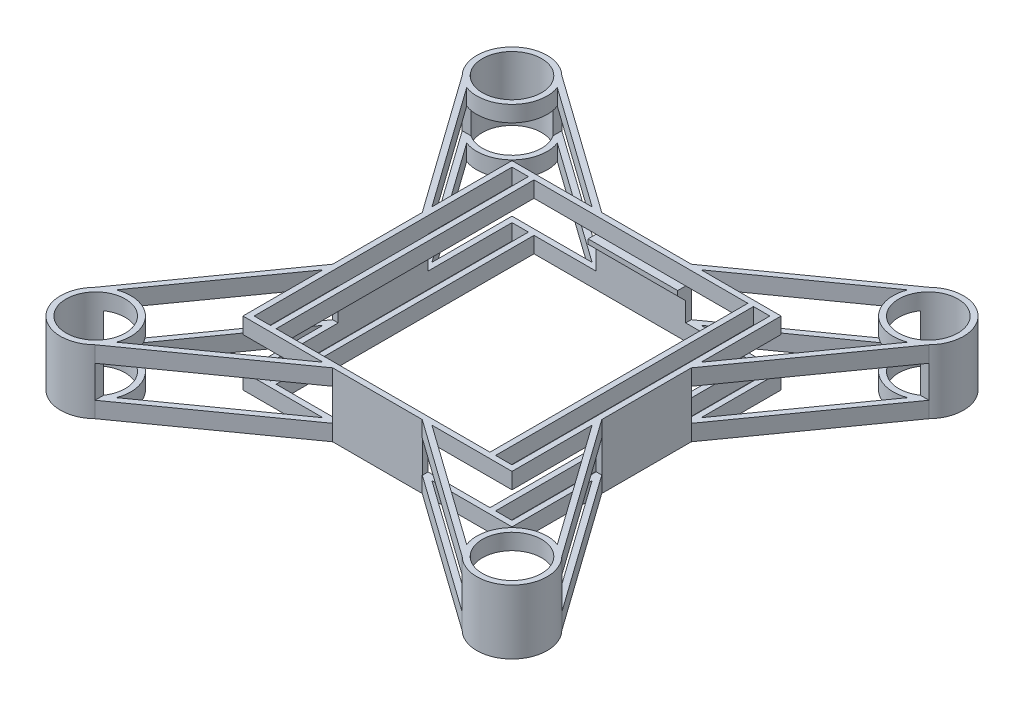
SolidWorks part; units mm, degrees
ref_plane "Front Plane" through (0, 0, 0) normal (0, 0, 1) x (1, 0, 0)
ref_plane "Top Plane" through (0, 0, 0) normal (0, 1, 0) x (1, 0, 0)
ref_plane "Right Plane" through (0, 0, 0) normal (1, 0, 0) x (0, 0, -1)
sketch "Sketch1" plane through (0, 0, 0) normal (0, 1, 0) x (1, 0, 0)
  line L0 (-20.3582, 15.0712) -> (-20.3582, 5.0712)
  line L1 (-19.6582, 14.3712) -> (-17.6082, 14.3712)
  line L2 (-19.6582, 14.3712) -> (-19.6582, -17.8288)
  line L3 (-19.6582, -17.8288) -> (-17.6082, -17.8288)
  line L4 (12.5418, 14.3712) -> (12.5418, -17.8288)
  line L5 (-20.3582, -18.5288) -> (-10.3582, -18.5288)
  line L6 (13.2418, 15.0712) -> (13.2418, 5.0712)
  line L7 (-20.3582, 15.0712) -> (-10.3582, 15.0712)
  line L8 (-16.9082, 14.3712) -> (-16.9082, -17.8288)
  line L9 (9.7918, 14.3712) -> (9.7918, -17.8288)
  line L10 (-17.6082, 14.3712) -> (-17.6082, -17.8288)
  line L11 (10.4918, 14.3712) -> (10.4918, -17.8288)
  line L12 (-16.9082, 14.3712) -> (9.7918, 14.3712)
  line L13 (-19.6582, 14.3712) -> (12.5418, 14.3712) construction
  line L14 (-16.9082, -17.8288) -> (9.7918, -17.8288)
  line L15 (-19.6582, -17.8288) -> (12.5418, -17.8288) construction
  line L16 (10.4918, -17.8288) -> (12.5418, -17.8288)
  line L17 (10.4918, 14.3712) -> (12.5418, 14.3712)
  line L18 (-20.3582, 15.0712) -> (-29.5506, 24.2636) construction
  line L19 (-32.1633, 21.6508) -> (-26.9378, 26.8763) construction
  line L20 (-31.0935, 20.1483) -> (-20.3582, 5.0712)
  line L21 (-25.4353, 25.8065) -> (-10.3582, 15.0712)
  line L22 (-32.7335, 21.2448) -> (-20.9284, 4.6652)
  line L23 (-26.5318, 27.4465) -> (-9.9522, 15.6414)
  line L24 (13.812, 4.6652) -> (13.2418, 3.8643)
  line L25 (-20.9284, 4.6652) -> (-20.3582, 3.8643)
  line L26 (2.8358, 15.6414) -> (2.035, 15.0712)
  line L27 (-9.9522, 15.6414) -> (-9.1513, 15.0712)
  line L28 (-3.5582, 27.4465) -> (-3.5582, -29.2492) construction
  line L29 (-32.1633, 21.6508) -> (-20.3582, 5.0712) construction
  line L30 (-26.9378, 26.8763) -> (-10.3582, 15.0712) construction
  line L31 (19.4154, 27.4465) -> (2.8358, 15.6414)
  line L32 (18.319, 25.8065) -> (3.2418, 15.0712)
  line L33 (25.6172, 21.2448) -> (13.812, 4.6652)
  line L34 (23.9771, 20.1483) -> (13.2418, 5.0712)
  line L35 (25.047, 21.6508) -> (19.8215, 26.8763) construction
  line L36 (13.2418, -1.7288) -> (-26.9378, -1.7288) construction
  line L37 (2.8358, -19.0991) -> (2.035, -18.5288)
  line L38 (18.319, -29.2642) -> (3.2418, -18.5288)
  line L39 (19.4154, -30.9042) -> (2.8358, -19.0991)
  line L40 (13.812, -8.1228) -> (13.2418, -7.322)
  line L41 (23.9771, -23.606) -> (13.2418, -8.5288)
  line L42 (25.6172, -24.7024) -> (13.812, -8.1228)
  line L43 (25.047, -25.1085) -> (19.8215, -30.334) construction
  line L44 (-9.9522, -19.0991) -> (-9.1513, -18.5288)
  line L45 (-25.4353, -29.2642) -> (-10.3582, -18.5288)
  line L46 (-26.5318, -30.9042) -> (-9.9522, -19.0991)
  line L47 (-32.1633, -25.1085) -> (-26.9378, -30.334) construction
  line L48 (-20.3582, -18.5288) -> (-29.5506, -27.7212) construction
  line L49 (-20.9284, -8.1228) -> (-20.3582, -7.322)
  line L50 (-32.7335, -24.7024) -> (-20.9284, -8.1228)
  line L51 (-31.0935, -23.606) -> (-20.3582, -8.5288)
  line L52 (-20.3582, -8.5288) -> (-20.3582, -18.5288)
  line L53 (-20.3582, 15.0712) -> (-20.3582, -18.5288) construction
  line L54 (-9.1513, -18.5288) -> (2.035, -18.5288)
  line L55 (-20.3582, -18.5288) -> (13.2418, -18.5288) construction
  line L56 (3.2418, -18.5288) -> (13.2418, -18.5288)
  line L57 (13.2418, -8.5288) -> (13.2418, -18.5288)
  line L58 (13.2418, 15.0712) -> (13.2418, -18.5288) construction
  line L59 (13.2418, 3.8643) -> (13.2418, -7.322)
  line L60 (3.2418, 15.0712) -> (13.2418, 15.0712)
  line L61 (-20.3582, 15.0712) -> (13.2418, 15.0712) construction
  line L62 (-9.1513, 15.0712) -> (2.035, 15.0712)
  line L63 (-20.3582, 3.8643) -> (-20.3582, -7.322)
  circle A0 centre (-29.5506, 24.2636) radius 3.695
  arc A1 (-31.0935, 20.1483) -> (-25.4353, 25.8065) centre (-29.5506, 24.2636) ccw
  circle A2 centre (-29.5506, 24.2636) radius 4.395 construction
  arc A3 (-26.4862, 27.4141) -> (-32.7011, 21.1992) centre (-29.5506, 24.2636) ccw
  arc A4 (19.3699, 27.4141) -> (25.5848, 21.1992) centre (22.4342, 24.2636) cw
  arc A5 (23.9771, 20.1483) -> (18.319, 25.8065) centre (22.4342, 24.2636) cw
  circle A6 centre (22.4342, 24.2636) radius 3.695
  circle A7 centre (22.4342, -27.7212) radius 3.695
  arc A8 (23.9771, -23.606) -> (18.319, -29.2642) centre (22.4342, -27.7212) ccw
  arc A9 (19.3699, -30.8718) -> (25.5848, -24.6569) centre (22.4342, -27.7212) ccw
  arc A10 (-26.4862, -30.8718) -> (-32.7011, -24.6569) centre (-29.5506, -27.7212) cw
  arc A11 (-31.0935, -23.606) -> (-25.4353, -29.2642) centre (-29.5506, -27.7212) cw
  circle A12 centre (-29.5506, -27.7212) radius 3.695
  point P8 (-3.5582, 14.3712)
  point P9 (-16.9082, 14.3712)
  point P10 (9.7918, 14.3712)
  point P11 (-3.5582, 14.3712)
  point P12 (-16.9082, 14.3712)
  point P23 (-20.3582, 5.0712)
  point P24 (-10.3582, 15.0712)
  point P28 (-29.5506, 24.2636)
  point P61 (22.4342, 24.2636)
  point P80 (22.4342, -27.7212)
  point P98 (-29.5506, -27.7212)
  point P99 (-20.3582, -8.5288)
  dimension "D9" = 7.39
  dimension "D1" = 32.2
  dimension "D2" = 32.2
  dimension "D4" = 13.35
  dimension "D5" = 13.35
  dimension "D8" = 13
  dimension "D10" = 10
  dimension "D11" = 10
  dimension "D12" = 90
  dimension "D16" = 26.7
  dimension "D3" = 0.7
  dimension "D6" = 0.7
  dimension "D7" = 0.7
  dimension "D13" = 0.7
  dimension "D14" = 0.7
  dimension "D15" = 0.7
extrude "Boss-Extrude1" add sketch "Sketch1" along normal blind 8 contours A10 L46 L44 L54 L37 L39 A9 L42 L40 L59 L24 L33 A4 L31 L26 L62 L27 L23 A3 L22 L25 L63 L49 L50 L41 A8 L38 L56 L57 A6 A5 L34 region at (-32.5975, 0, -27.3105)
sketch "Sketch2" plane through (-20.3582, 0, 0) normal (-1, 0, 0) x (0, 0, 1)
  line L0 (-21.1992, 8) -> (-21.1992, 0) construction
  line L1 (24.6569, 8) -> (24.6569, 0) construction
  line L2 (-21.1992, 4) -> (24.6569, 4)
  line L3 (-21.1992, 4) -> (-21.1992, 6)
  line L4 (-21.1992, 6) -> (24.6569, 6)
  line L5 (24.6569, 4) -> (24.6569, 6)
  line L7 (-21.1992, 4) -> (24.6569, 4)
  line L8 (-21.1992, 4) -> (-21.1992, 2)
  line L9 (-21.1992, 2) -> (24.6569, 2)
  line L10 (24.6569, 4) -> (24.6569, 2)
  point P0 (-21.1992, 4)
  line M4 (7.322, 0) -> (7.322, 8)
  line M6 (-3.8643, 8) -> (-3.8643, 0)
  dimension "D1" = 2
  dimension "D2" = 2
extrude "Cut-Extrude1" cut sketch "Sketch2" against normal through all both and the other way through all contours L4 L3 L2 M6 | L4 L2 M6 M4 | L2 L5 L4 M4 | L8 L9 L2 M6 | L9 L2 M6 M4 | L10 L2 L9 M4 region at (-20.3582, 5, -12.5318) region at (-20.3582, 3, -12.5318) region at (-20.3582, 5, 1.7288) region at (-20.3582, 3, 1.7288) region at (-20.3582, 5, 15.9894) region at (-20.3582, 3, 15.9894)
sketch "Sketch5" plane through (0, 0, -15.0712) normal (0, 0, -1) x (-1, 0, 0)
  line L0 (-19.3699, 8) -> (-19.3699, 0) construction
  line L1 (-19.3699, 4) -> (26.4862, 4)
  line L2 (-19.3699, 4) -> (-19.3699, 6)
  line L3 (-19.3699, 6) -> (26.4862, 6)
  line L4 (26.4862, 4) -> (26.4862, 6)
  line L5 (26.4862, 8) -> (26.4862, 0) construction
  line L7 (-19.3699, 4) -> (26.4862, 4)
  line L8 (-19.3699, 4) -> (-19.3699, 2)
  line L9 (-19.3699, 2) -> (26.4862, 2)
  line L10 (26.4862, 4) -> (26.4862, 2)
  line M2 (-2.035, 6) -> (9.1513, 6)
extrude "Cut-Extrude2" cut sketch "Sketch5" against normal through all both and the other way through all contours L1 L4 L3 L2 M2 | L10 L1 L8 L9 region at (-3.5582, 5, -15.0712) region at (-3.5582, 3, -15.0712)
sketch "Sketch6" plane through (0, 2, 0) normal (0, 1, 0) x (1, 0, 0)
  line L0 (-19.6582, 14.3712) -> (-19.6582, -17.8288) construction
  line L1 (-20.3582, 3.8643) -> (-19.6582, 3.8643)
  line L2 (-20.3582, 3.8643) -> (-20.3582, -7.3252)
  line L3 (-20.3582, -7.3252) -> (-19.6582, -7.3252)
  line L4 (-19.6582, 3.8643) -> (-19.6582, -7.3252)
  line L5 (-16.9082, -17.8288) -> (9.7918, -17.8288) construction
  line L6 (-9.1513, -18.5288) -> (2.0681, -18.5288)
  line L7 (-9.1513, -18.5288) -> (-9.1513, -17.8288)
  line L8 (-9.1513, -17.8288) -> (2.0681, -17.8288)
  line L9 (2.0681, -18.5288) -> (2.0681, -17.8288)
  line L10 (12.5418, 14.3712) -> (12.5418, -17.8288) construction
  line L11 (13.2418, -7.322) -> (12.5418, -7.322)
  line L12 (13.2418, -7.322) -> (13.2418, 3.8643)
  line L13 (13.2418, 3.8643) -> (12.5418, 3.8643)
  line L14 (12.5418, -7.322) -> (12.5418, 3.8643)
  line L15 (-16.9082, 14.3712) -> (9.7918, 14.3712) construction
  line L16 (-9.1513, 15.0712) -> (2.035, 15.0712)
  line L17 (-9.1513, 15.0712) -> (-9.1513, 14.3712)
  line L18 (-9.1513, 14.3712) -> (2.035, 14.3712)
  line L19 (2.035, 15.0712) -> (2.035, 14.3712)
extrude "Boss-Extrude2" add sketch "Sketch6" along normal up to surface (4 mm away) up to face at (-3.5582, 6, 1.7288)
sketch "Sketch7" plane through (0, 0, -14.3712) normal (0, 0, 1) x (1, 0, 0)
  line L0 (2.035, 6) -> (2.035, 2) construction
  line L1 (-9.1513, 6) -> (2.035, 6)
  line L2 (-9.1513, 6) -> (-9.1513, 5.4)
  line L3 (-9.1513, 5.4) -> (2.035, 5.4)
  line L4 (2.035, 6) -> (2.035, 5.4)
  dimension "D1" = 0.6
extrude "Boss-Extrude3" add sketch "Sketch7" along normal blind 1
chamfer "Chamfer1" distance 1 angle 45 1 edges at (-3.5582, 5.4, -14.3712)
sketch "Sketch8" plane through (0, 0, 17.8288) normal (0, 0, -1) x (-1, 0, 0)
  line L0 (9.1513, 6) -> (9.1513, 2) construction
  line L1 (-2.0681, 6) -> (9.1513, 6)
  line L2 (-2.0681, 6) -> (-2.0681, 5.4)
  line L3 (-2.0681, 5.4) -> (9.1513, 5.4)
  line L4 (9.1513, 6) -> (9.1513, 5.4)
  dimension "D1" = 0.6
extrude "Boss-Extrude4" add sketch "Sketch8" along normal blind 1
chamfer "Chamfer2" distance 1 angle 45 1 edges at (-3.5416, 5.4, 17.8288)
sketch "Sketch9" plane through (0, 0, 24.6569) normal (0, 0, -1) x (-1, 0, 0)
  line L1 (-20.3695, 6) -> (-19.3699, 6)
  line L2 (-20.3695, 6) -> (-20.3695, 2)
  line L3 (-20.3695, 2) -> (-19.3699, 2)
  line L4 (-19.3699, 6) -> (-19.3699, 2)
extrude "Cut-Extrude3" cut sketch "Sketch9" along direction (0, 0, 1) on the side against the normal up to surface (0.9996 mm away) up to face at (22.4342, 4, 24.3416)
sketch "Sketch10" plane through (-26.4862, 0, 0) normal (1, 0, 0) x (0, 0, -1)
  line L1 (-25.6565, 6) -> (-24.6569, 6)
  line L2 (-25.6565, 6) -> (-25.6565, 2)
  line L3 (-25.6565, 2) -> (-24.6569, 2)
  line L4 (-24.6569, 6) -> (-24.6569, 2)
extrude "Cut-Extrude4" cut sketch "Sketch10" against normal up to surface (0.9996 mm away) up to face at (-29.5506, 0, 31.4162)
sketch "Sketch11" plane through (-26.4862, 0, 0) normal (1, 0, 0) x (0, 0, -1)
  line L1 (21.1992, 6) -> (22.1989, 6)
  line L2 (21.1992, 6) -> (21.1992, 2)
  line L3 (21.1992, 2) -> (22.1989, 2)
  line L4 (22.1989, 6) -> (22.1989, 2)
extrude "Cut-Extrude5" cut sketch "Sketch11" against normal up to surface up to face at (-29.5506, 4, -20.8839)
sketch "Sketch12" plane through (0, 0, -21.1992) normal (0, 0, 1) x (1, 0, 0)
  line L1 (19.3699, 6) -> (20.3695, 6)
  line L2 (19.3699, 6) -> (19.3699, 2)
  line L3 (19.3699, 2) -> (20.3695, 2)
  line L4 (20.3695, 6) -> (20.3695, 2)
extrude "Cut-Extrude6" cut sketch "Sketch12" against normal up to surface up to face at (22.4342, 0, -20.5686)
